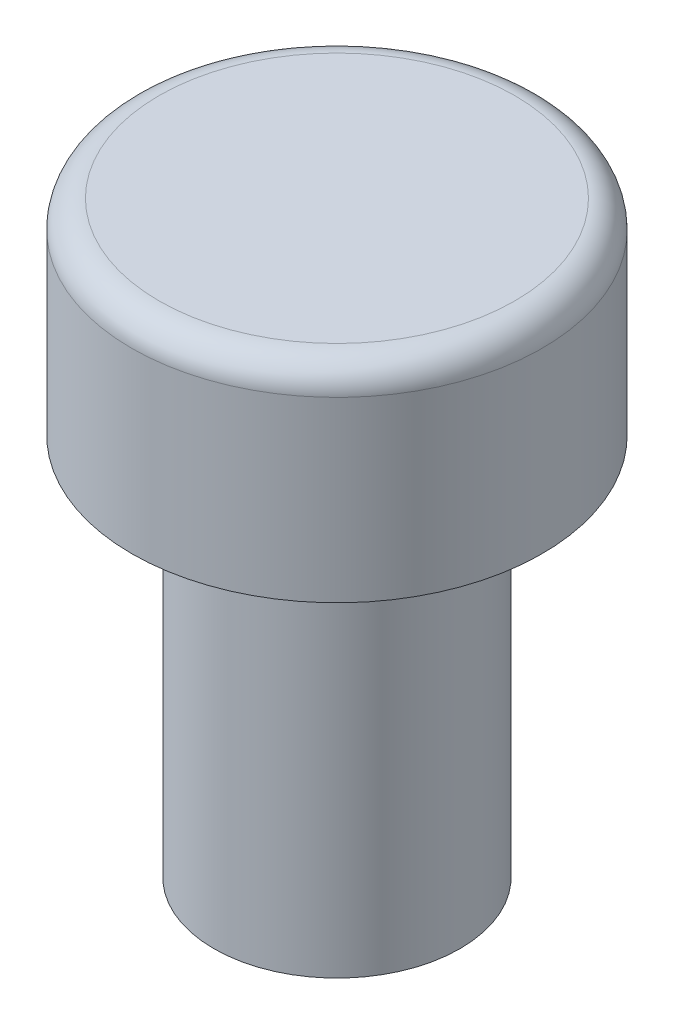
SolidWorks part; units mm, degrees
ref_plane "Front Plane" through (0, 0, 0) normal (0, 0, 1) x (1, 0, 0)
ref_plane "Top Plane" through (0, 0, 0) normal (0, 1, 0) x (1, 0, 0)
ref_plane "Right Plane" through (0, 0, 0) normal (1, 0, 0) x (0, 0, -1)
sketch "Sketch1" plane through (0, 0, 0) normal (0, 1, 0) x (1, 0, 0)
  circle A0 centre (0, 0) radius 7.5
  dimension "D1" = 15
extrude "Boss-Extrude1" add sketch "Sketch1" along normal blind 7.5
fillet "Fillet1" radius 1 1 edges at (0, 7.5, 7.5)
sketch "Sketch2" plane through (0, 0, 0) normal (0, -1, 0) x (1, 0, 0)
  circle A0 centre (0, 0) radius 4.5
  dimension "D1" = 9
extrude "Boss-Extrude2" add sketch "Sketch2" along normal blind 14
sketch "Sketch3" plane through (0, -14, 0) normal (0, -1, 0) x (-1, 0, 0)
  circle A0 centre (0, 0) radius 3.125
  dimension "D1" = 6.25
extrude "Cut-Extrude1" cut sketch "Sketch3" against normal blind 11
sketch "Sketch4" plane through (0, -3, 0) normal (0, -1, 0) x (-1, 0, 0)
  line L0 (1.75, -2.589) -> (1.75, 2.589)
  circle A0 centre (0, 0) radius 3.125 construction
  circle A1 centre (0, 0) radius 3.125
  circle M2 centre (0, 0) radius 3.125
  dimension "D1" = 1.75
  dimension "D2" = 6.25
extrude "Boss-Extrude3" add sketch "Sketch4" along normal up to surface (11 mm away) contours L0 M2 region at (-2.3119, -3, 0) up to face at (0, -14, -3.125)
